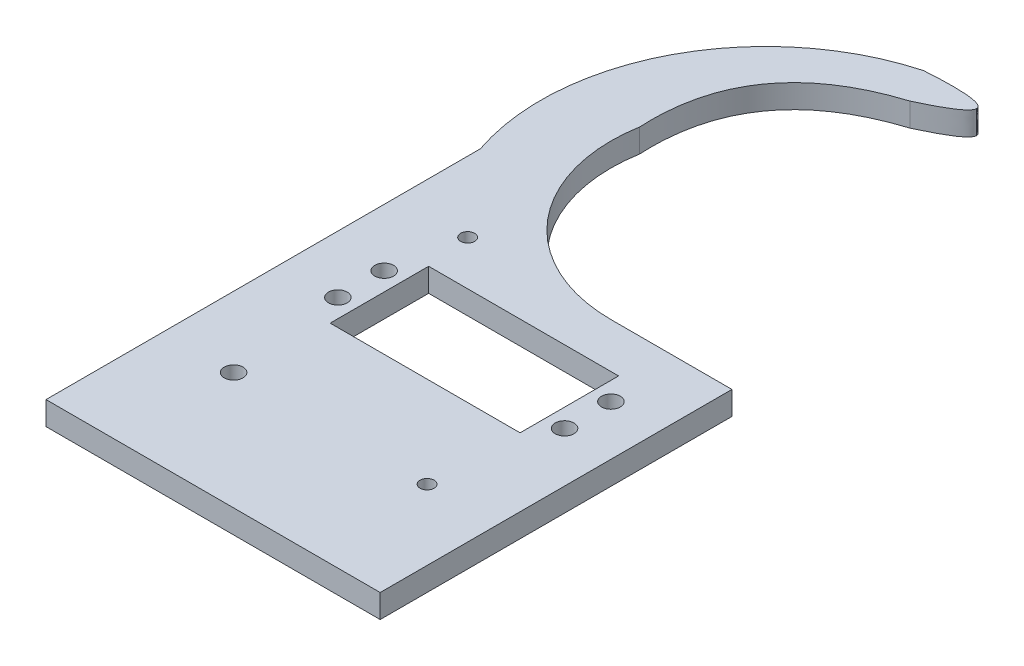
SolidWorks part; units mm, degrees
ref_plane "Front Plane" through (0, 0, 0) normal (0, 0, 1) x (1, 0, 0)
ref_plane "Top Plane" through (0, 0, 0) normal (0, 1, 0) x (1, 0, 0)
ref_plane "Right Plane" through (0, 0, 0) normal (1, 0, 0) x (0, 0, -1)
sketch "Sketch1" plane through (0, 0, 0) normal (0, 1, 0) x (1, 0, 0)
  line L0 (0, 48) -> (0, 33)
  line L1 (-45.4667, 13.2678) -> (5.0067, 13.2678)
  line L2 (-45.4667, 13.2678) -> (-45.4667, -47.4725)
  line L3 (-45.4667, -47.4725) -> (5.0067, -47.4725)
  line L4 (5.0067, 13.2678) -> (5.0067, -47.4725)
  line L5 (-45.4667, -33) -> (25.7862, -33)
  line L6 (-45.4667, -33) -> (-45.4667, -107.9997)
  line L7 (-45.4667, -107.9997) -> (25.7862, -107.9997)
  line L8 (25.7862, -33) -> (25.7862, -107.9997)
  line L9 (0, -33) -> (0, -48)
  circle A0 centre (0, 0) radius 33
  circle A1 centre (0, 0) radius 48
  dimension "D1" = 66
  dimension "D2" = 96
extrude "Boss-Extrude1" add sketch "Sketch1" along normal mid plane 5 contours L1 A1 L2 L5 A0 | L0 A1 L1 A0 | A1 L5 L2 L3 L4 | A1 L4 L3 L6 L7 L8 | L4 A1 L8 L5 | L5 A1 L9 | L9 A1 L4 L5 | A1 L2 L5 region at (-23.9398, 0, -29.2891) region at (-42.2017, 0, 27.6591) region at (-34.5365, 0, 12.6244) region at (14.2581, 0, 39.2676) region at (-9.4959, 0, 77.3893) region at (-33.8325, 0, 41.6832) region at (-13.4692, 0, 39.0285) region at (2.5033, 0, 40.2363)
sketch "Sketch2" plane through (0, 2.5, 0) normal (0, 1, 0) x (1, 0, 0)
  line L1 (-29.2862, -42.5955) -> (9.7138, -42.5955)
  line L2 (-29.2862, -42.5955) -> (-29.2862, -61.5955)
  line L3 (-29.2862, -61.5955) -> (9.7138, -61.5955)
  line L4 (9.7138, -42.5955) -> (9.7138, -61.5955)
  dimension "D1" = 39
  dimension "D2" = 19
extrude "Cut-Extrude2" cut sketch "Sketch2" against normal through all
sketch "Sketch6" plane through (0, 2.5, 0) normal (0, 1, 0) x (1, 0, 0)
  line L0 (-9.7862, -61.5955) -> (-9.7862, -104.4039) construction
  line L1 (-29.2862, -61.5955) -> (9.7138, -61.5955) construction
  line L2 (-9.7862, -82.9997) -> (25.7862, -82.9997) construction
  line L3 (25.7862, -33) -> (25.7862, -107.9997) construction
  line L4 (25.7862, -82.9997) -> (-45.4667, -82.9997) construction
  line L5 (-45.4667, -15.3875) -> (-45.4667, -107.9997) construction
  line L6 (9.7138, -42.5955) -> (-29.2862, -42.5955) construction
  line L7 (-45.4667, -107.9997) -> (25.7862, -107.9997) construction
  circle A0 centre (10.7862, -82.9997) radius 1.5
  circle A1 centre (-30.4667, -82.9997) radius 2
  circle A2 centre (-30.4667, -33.0955) radius 1.5
  dimension "D1" = 3
  dimension "D2" = 15
  dimension "D3" = 4
  dimension "D5" = 3
  dimension "D6" = 15
  dimension "D8" = 9.5
  dimension "D9" = 25
  dimension "D4" = 15
  dimension "D7" = 25
extrude "Cut-Extrude11" cut sketch "Sketch6" against normal through all
sketch "Sketch8" plane through (0, 2.5, 0) normal (0, 1, 0) x (1, 0, 0)
  line L1 (-29.2862, -61.5955) -> (9.8785, -61.5955)
  line L2 (-29.2862, -61.5955) -> (-29.2862, -63.5955)
  line L3 (-29.2862, -63.5955) -> (9.8785, -63.5955)
  line L4 (9.8785, -61.5955) -> (9.8785, -63.5955)
  dimension "D1" = 2
extrude "Cut-Extrude12" cut sketch "Sketch8" against normal blind 10
sketch "Sketch9" plane through (0, 2.5, 0) normal (0, 1, 0) x (1, 0, 0)
  line L1 (-29.2862, -42.5955) -> (11.2138, -42.5955)
  line L2 (-29.2862, -42.5955) -> (-29.2862, -63.5955)
  line L3 (-29.2862, -63.5955) -> (11.2138, -63.5955)
  line L4 (11.2138, -42.5955) -> (11.2138, -63.5955)
  dimension "D1" = 40.5
  dimension "D2" = 21
extrude "Cut-Extrude14" cut sketch "Sketch9" against normal blind 10
sketch "Sketch11" plane through (0, 2.5, 0) normal (0, 1, 0) x (1, 0, 0)
  line L0 (-8.4912, 43.9058) -> (-8.4912, 31.8889) construction
  line L1 (-8.4912, 39.2208) -> (-8.4912, 31.8889)
  line L2 (-8.4912, 31.8889) -> (-32.514, 5.6424)
  arc A2 (0, 33) -> (0, -33) centre (0, 0) ccw construction
  spline S0 degree 2 poles (-32.514, 5.6424) (-33.8828, 31.2071) (-8.4912, 39.2208) knots 0 0 0 1 1 1
extrude "Cut-Extrude17" cut sketch "Sketch11" against normal blind 10
sketch "Sketch10" plane through (0, 2.5, 0) normal (0, 1, 0) x (1, 0, 0)
  line L0 (-29.2862, -42.5955) -> (-29.2862, -48.1555)
  line L1 (-29.2862, -42.5955) -> (-29.2862, -63.5955) construction
  line L2 (-29.2862, -48.1555) -> (-33.2062, -48.1555)
  line L3 (11.2138, -53.0955) -> (-29.2862, -53.0955)
  line L4 (11.2138, -63.5955) -> (11.2138, -42.5955) construction
  line L5 (-9.0362, -42.5955) -> (-9.0362, -63.5955)
  line L6 (11.2138, -42.5955) -> (-29.2862, -42.5955) construction
  line L7 (-29.2862, -63.5955) -> (11.2138, -63.5955) construction
  circle A0 centre (-33.2062, -48.1555) radius 2
  circle A1 centre (-33.2062, -58.0355) radius 2
  circle A2 centre (15.1338, -58.0355) radius 2
  circle A3 centre (15.1338, -48.1555) radius 2
  dimension "D3" = 4
  dimension "D1" = 5.56
  dimension "D2" = 3.92
extrude "Cut-Extrude16" cut sketch "Sketch10" against normal blind 10 contours A0 | A1 | A3 | A2 region at (-35.1497, 2.5, 48.1555) region at (-33.2062, 2.5, 58.0355) region at (15.1338, 2.5, 58.0355) region at (15.1338, 2.5, 48.1555)
sketch "Sketch16" plane through (0, 2.5, 0) normal (0, 1, 0) x (1, 0, 0)
  line L4 (0, 48) -> (0, 33) construction
  line L5 (-12.6738, 46.2966) -> (-14.0893, 56.8471)
  line L6 (-14.0893, 56.8471) -> (1.9936, 53.8947)
  line L7 (0, 48) -> (0, 33)
  line L8 (1.9936, 53.8947) -> (6.6165, 45.5036)
  line L9 (6.6165, 45.5036) -> (5.2957, 36.5687)
  line L10 (5.2957, 36.5687) -> (3.1202, 30.8192)
  line L11 (3.1202, 30.8192) -> (-12.2635, 30.8192)
  line L12 (-12.2635, 30.8192) -> (-8.4912, 39.2208)
  arc A0 (0, 48) -> (-45.4667, -15.3875) centre (0, 0) ccw construction
  spline S0 degree 2 poles (-8.4912, 39.2208) (10.3763, 47.8692) (-12.6738, 46.2966) knots 0 0 0 1 1 1
  line M5 (-8.4912, 39.2208) -> (-8.4912, 31.8889)
  arc M6 (-8.4912, 31.8889) -> (0, 33) centre (0, 0) cw
  line M7 (0, 33) -> (0, 48)
  arc M8 (0, 48) -> (-45.4667, -15.3875) centre (0, 0) ccw
extrude "Cut-Extrude23" cut sketch "Sketch16" against normal blind 10 contours S0 L12 L11 L10 L9 L8 L6 L5 M7 M6 M5 M8 | S0 M7 M8 | S0 M5 M6 M7 region at (-4.2139, 2.5, -46.9873) region at (-13.0519, 2.5, -51.6161) region at (-3.9352, 2.5, -37.1638)
